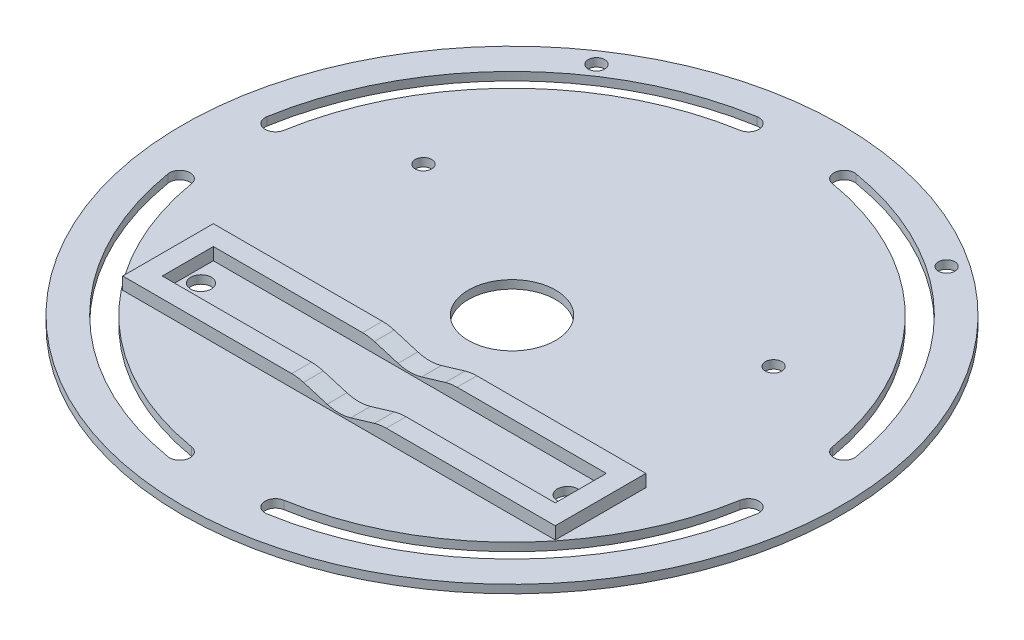
SolidWorks part; units mm, degrees
ref_plane "Front Plane" through (0, 0, 0) normal (0, 0, 1) x (1, 0, 0)
ref_plane "Top Plane" through (0, 0, 0) normal (0, 1, 0) x (1, 0, 0)
ref_plane "Right Plane" through (0, 0, 0) normal (1, 0, 0) x (0, 0, -1)
sketch "Sketch1" plane through (0, 0, 0) normal (0, 1, 0) x (1, 0, 0)
  circle A0 centre (0, 0) radius 80
  dimension "D1" = 160
extrude "Boss-Extrude1" add sketch "Sketch1" along normal blind 2
sketch "Sketch2" plane through (0, 2, 0) normal (0, 1, 0) x (1, 0, 0)
  line L0 (0, 67.5) -> (0, 72.5) construction
  line L1 (0, 0) -> (66.9225, 8.8105) construction
  line L2 (0, 0) -> (66.9225, -8.8105) construction
  line L3 (67.5, 0) -> (72.5, 0) construction
  line L4 (-9.131, 69.3569) -> (-9.1368, 69.4011)
  line L5 (9.131, 69.3569) -> (9.1368, 69.4011)
  line L6 (0, 0) -> (-8.8105, 66.9225) construction
  line L7 (0, 0) -> (8.8105, 66.9225) construction
  line L8 (-9.1368, 69.4011) -> (-9.4631, 71.8798) construction
  line L9 (-8.8105, 66.9225) -> (-9.131, 69.3569) construction
  line L10 (9.1368, 69.4011) -> (9.4631, 71.8798) construction
  line L11 (8.8105, 66.9225) -> (9.131, 69.3569) construction
  line L12 (0, 0) -> (8.8105, -66.9225) construction
  line L13 (0, 0) -> (-8.8105, -66.9225) construction
  line L14 (0, -67.5) -> (0, -72.5) construction
  line L15 (0, 0) -> (-66.9225, -8.8105) construction
  line L16 (0, 0) -> (-66.9225, 8.8105) construction
  line L17 (-67.5, 0) -> (-72.5, 0) construction
  circle A0 centre (0, 0) radius 70 construction
  arc A1 (-12.0242, 71.4959) -> (-71.4959, 12.0242) centre (0, 0) ccw
  arc A2 (-11.195, 66.5652) -> (-66.5652, 11.195) centre (0, 0) ccw
  arc A4 (-11.195, 66.5652) -> (-12.0242, 71.4959) centre (-11.6096, 69.0305) ccw
  arc A5 (-12.0242, 71.4959) -> (-14.0672, 68.572) centre (-11.6096, 69.0305) ccw construction
  arc A6 (-14.0672, 68.572) -> (-11.195, 66.5652) centre (-11.6096, 69.0305) ccw construction
  arc A7 (11.195, 66.5652) -> (12.0242, 71.4959) centre (11.6096, 69.0305) cw
  arc A8 (-8.8105, 66.9225) -> (-11.195, 66.5652) centre (0, 0) ccw construction
  circle A9 centre (0, 0) radius 67.5 construction
  arc A10 (0, 67.5) -> (-8.8105, 66.9225) centre (0, 0) ccw construction
  arc A11 (8.8105, 66.9225) -> (0, 67.5) centre (0, 0) ccw construction
  arc A12 (11.195, 66.5652) -> (8.8105, 66.9225) centre (0, 0) ccw construction
  arc A13 (12.0242, 71.4959) -> (9.4631, 71.8798) centre (0, 0) ccw construction
  circle A14 centre (0, 0) radius 72.5 construction
  arc A15 (9.4631, 71.8798) -> (0, 72.5) centre (0, 0) ccw construction
  arc A16 (0, 72.5) -> (-9.4631, 71.8798) centre (0, 0) ccw construction
  arc A17 (-9.4631, 71.8798) -> (-12.0242, 71.4959) centre (0, 0) ccw construction
  arc A18 (68.572, 14.0672) -> (66.5652, 11.195) centre (69.0305, 11.6096) ccw construction
  arc A19 (71.4959, 12.0242) -> (68.572, 14.0672) centre (69.0305, 11.6096) ccw construction
  arc A20 (66.5652, 11.195) -> (71.4959, 12.0242) centre (69.0305, 11.6096) ccw
  arc A21 (66.5652, -11.195) -> (71.4959, -12.0242) centre (69.0305, -11.6096) cw
  arc A22 (14.0672, -68.572) -> (11.195, -66.5652) centre (11.6096, -69.0305) ccw construction
  arc A23 (12.0242, -71.4959) -> (14.0672, -68.572) centre (11.6096, -69.0305) ccw construction
  arc A24 (11.195, -66.5652) -> (12.0242, -71.4959) centre (11.6096, -69.0305) ccw
  arc A25 (-11.195, -66.5652) -> (-12.0242, -71.4959) centre (-11.6096, -69.0305) cw
  arc A26 (-68.572, -14.0672) -> (-66.5652, -11.195) centre (-69.0305, -11.6096) ccw construction
  arc A27 (-71.4959, -12.0242) -> (-68.572, -14.0672) centre (-69.0305, -11.6096) ccw construction
  arc A28 (-66.5652, -11.195) -> (-71.4959, -12.0242) centre (-69.0305, -11.6096) ccw
  arc A29 (-66.5652, 11.195) -> (-71.4959, 12.0242) centre (-69.0305, 11.6096) cw
  arc A30 (66.9225, 8.8105) -> (66.5652, 11.195) centre (0, 0) ccw construction
  arc A31 (66.5652, 11.195) -> (11.195, 66.5652) centre (0, 0) ccw
  arc A32 (67.5, 0) -> (66.9225, 8.8105) centre (0, 0) ccw construction
  arc A33 (66.9225, -8.8105) -> (67.5, 0) centre (0, 0) ccw construction
  arc A34 (66.5652, -11.195) -> (66.9225, -8.8105) centre (0, 0) ccw construction
  arc A35 (71.4959, -12.0242) -> (72.5, 0) centre (0, 0) ccw construction
  arc A36 (71.4959, 12.0242) -> (12.0242, 71.4959) centre (0, 0) ccw
  arc A37 (72.5, 0) -> (71.4959, 12.0242) centre (0, 0) ccw construction
  arc A38 (8.8105, -66.9225) -> (11.195, -66.5652) centre (0, 0) ccw construction
  arc A39 (11.195, -66.5652) -> (66.5652, -11.195) centre (0, 0) ccw
  arc A40 (0, -67.5) -> (8.8105, -66.9225) centre (0, 0) ccw construction
  arc A41 (-8.8105, -66.9225) -> (0, -67.5) centre (0, 0) ccw construction
  arc A42 (-11.195, -66.5652) -> (-8.8105, -66.9225) centre (0, 0) ccw construction
  arc A43 (-12.0242, -71.4959) -> (0, -72.5) centre (0, 0) ccw construction
  arc A44 (12.0242, -71.4959) -> (71.4959, -12.0242) centre (0, 0) ccw
  arc A45 (0, -72.5) -> (12.0242, -71.4959) centre (0, 0) ccw construction
  arc A46 (-66.5652, 11.195) -> (-66.9225, 8.8105) centre (0, 0) ccw construction
  arc A47 (-66.5652, -11.195) -> (-11.195, -66.5652) centre (0, 0) ccw
  arc A48 (-66.9225, 8.8105) -> (-67.5, 0) centre (0, 0) ccw construction
  arc A49 (-67.5, 0) -> (-66.9225, -8.8105) centre (0, 0) ccw construction
  arc A50 (-66.9225, -8.8105) -> (-66.5652, -11.195) centre (0, 0) ccw construction
  arc A51 (-72.5, 0) -> (-71.4959, -12.0242) centre (0, 0) ccw construction
  arc A52 (-71.4959, -12.0242) -> (-12.0242, -71.4959) centre (0, 0) ccw
  arc A53 (-71.4959, 12.0242) -> (-72.5, 0) centre (0, 0) ccw construction
  point P60 (0, 0)
  dimension "D1" = 140
  dimension "D4" = 15
  dimension "D5" = 7.5
  dimension "D2" = 2.5
  dimension "D3" = 2.5
  dimension "D6" = 4
extrude "Cut-Extrude1" cut sketch "Sketch2" against normal blind 2 contours A28 A52 A25 A47 | A29 A2 A4 A1 | A24 A44 A21 A39 | A20 A36 A7 A31 region at (-10.6482, 2, -70.331) region at (10.3092, 2, -68.0691) region at (69.2988, 2, 10.0148) region at (-10.0148, 2, 69.2988)
sketch "Sketch3" plane through (0, 2, 0) normal (0, 1, 0) x (1, 0, 0)
  line L0 (0, 0) -> (0, -31) construction
  line L1 (0, -31) -> (-44.5, -31) construction
  line L2 (0, -31) -> (44.5, -31) construction
  circle A0 centre (-44.5, -31) radius 2.5
  circle A1 centre (44.5, -31) radius 2.5
  dimension "D4" = 5
  dimension "D5" = 5
  dimension "D1" = 44.5
  dimension "D2" = 44.5
  dimension "D3" = 31
extrude "Cut-Extrude2" cut sketch "Sketch3" against normal through all
sketch "Sketch4" plane through (0, 2, 0) normal (0, 1, 0) x (1, 0, 0)
  line L0 (-44.5, -31) -> (44.5, -31) construction
  line L1 (-52.5, -42) -> (-52.5, -20)
  line L2 (-47.5, -37) -> (47.5, -37)
  line L3 (-47.5, -37) -> (-47.5, -25)
  line L4 (-47.5, -25) -> (47.5, -25)
  line L5 (47.5, -37) -> (47.5, -25)
  line L6 (-47.5, -37) -> (47.5, -25) construction
  line L7 (-47.5, -25) -> (47.5, -37) construction
  line L8 (-52.5, -20) -> (52.5, -20)
  line L9 (52.5, -42) -> (52.5, -20)
  line L10 (-52.5, -42) -> (52.5, -42)
  point P4 (0, -31)
  dimension "D1" = 12
  dimension "D2" = 95
  dimension "D3" = 5
extrude "Boss-Extrude2" add sketch "Sketch4" along normal blind 3
sketch "Sketch5" plane through (0, 0, 42) normal (0, 0, 1) x (1, 0, 0)
  line L0 (0, 5) -> (0, 2) construction
  line L1 (-52.5, 5) -> (52.5, 5) construction
  line L2 (-52.5, 2) -> (52.5, 2) construction
  line L3 (0, 2) -> (-10, 5)
  line L4 (-10, 5) -> (10, 5)
  line L5 (10, 5) -> (0, 2)
  point P6 (0, 5)
  dimension "D1" = 20
extrude "Cut-Extrude3" cut sketch "Sketch5" against normal through all
fillet "Fillet1" radius 10 6 edges at (10, 5, 39.5) (10, 5, 22.5) (0, 2, 22.5) (0, 2, 39.5) (-10, 5, 39.5) (-10, 5, 22.5)
sketch "Sketch6" plane through (0, 2, 0) normal (0, 1, 0) x (1, 0, 0)
  line L0 (-47.5, 66) -> (-47.5, 16) construction
  line L1 (-47.5, 66) -> (47.5, 66) construction
  line L2 (47.5, 16) -> (47.5, 66) construction
  line L3 (-47.5, 16) -> (47.5, 16) construction
  line L4 (0, -2.75) -> (0, 2.75) construction
  line L5 (-47.5, 16) -> (-27.5, 16) construction
  line L6 (-27.5, 16) -> (-27.5, 31) construction
  line L7 (-27.5, 31) -> (27.5, 31) construction
  line L8 (27.5, 31) -> (27.5, 16) construction
  line L9 (27.5, 16) -> (47.5, 16) construction
  line L10 (0, 31) -> (0, 0) construction
  circle A2 centre (42.5, 63) radius 2
  circle A3 centre (42.5, 21) radius 2
  circle A4 centre (-42.5, 21) radius 2
  circle A5 centre (-42.5, 63) radius 2
  dimension "D10" = 4
  dimension "D2" = 50
  dimension "D3" = 95
  dimension "D4" = 31
  dimension "D5" = 15
  dimension "D6" = 3
  dimension "D7" = 20
  dimension "D8" = 5
  dimension "D9" = 20
  dimension "D11" = 5
  dimension "D12" = 5
extrude "Cut-Extrude4" cut sketch "Sketch6" against normal through all
other "Move Face1" flip direction yes face at (47.5, 3.5, 31) face at (0, 3.6971, 37) face at (-47.5, 3.5, 31) face at (0, 3.6971, 25) offset 0.2 parameters "D1"=0.2
sketch "Sketch7" plane through (0, 2, 0) normal (0, 1, 0) x (1, 0, 0)
  circle A0 centre (0, 0) radius 10.6
  dimension "D1" = 21.2
extrude "Cut-Extrude5" cut sketch "Sketch7" against normal through all
